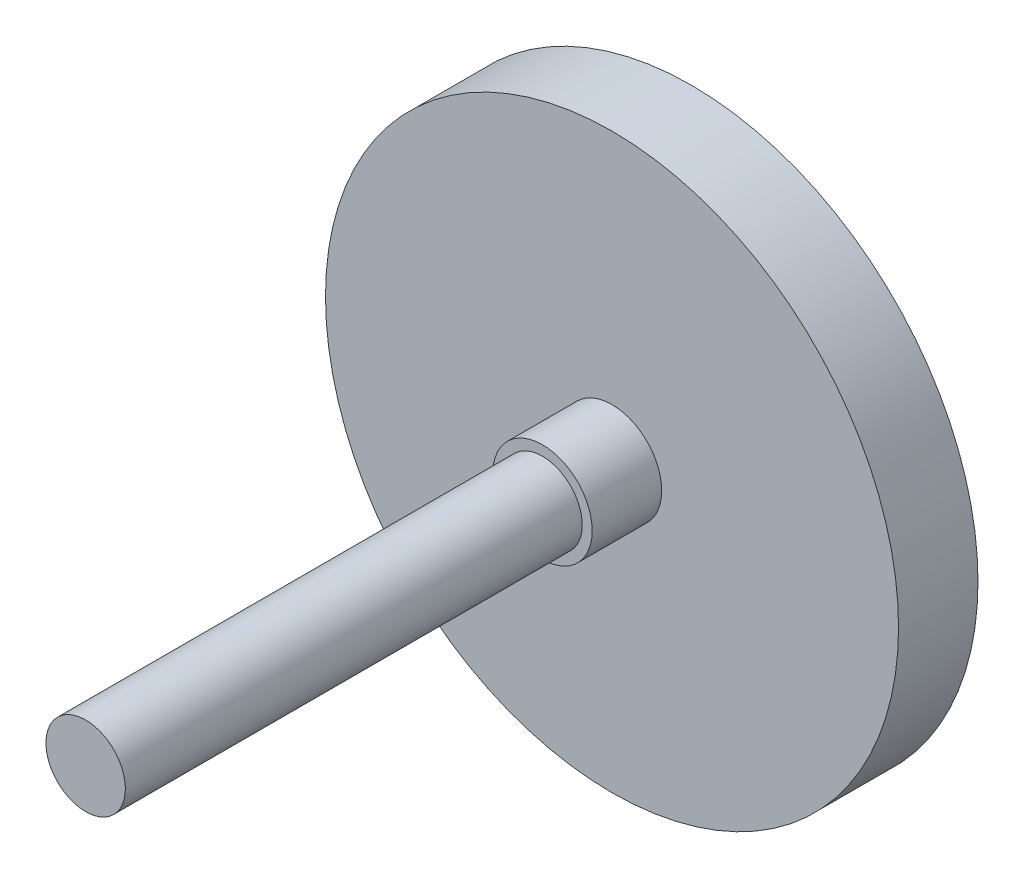
SolidWorks part; units mm, degrees
ref_plane "Plan de face" through (0, 0, 0) normal (0, 0, 1) x (1, 0, 0)
ref_plane "Plan de dessus" through (0, 0, 0) normal (0, 1, 0) x (1, 0, 0)
ref_plane "Plan de droite" through (0, 0, 0) normal (1, 0, 0) x (0, 0, -1)
sketch "Esquisse1" plane through (0, 0, 0) normal (0, 0, 1) x (1, 0, 0)
  circle A0 centre (0, 0) radius 28.85
extrude "Boss.-Extru.1" add sketch "Esquisse1" along normal blind 8
sketch "Esquisse2" plane through (0, 0, 8) normal (0, 0, 1) x (1, 0, 0)
  circle A0 centre (0, 0) radius 4
  circle A1 centre (0, 0) radius 5
sketch "Esquisse3" plane through (0, 0, 0) normal (0, 0, -1) x (-1, 0, 0)
  circle A0 centre (0, 0) radius 4
extrude "Enlèv. mat.-Extru.1" cut sketch "Esquisse3" against normal blind 2
extrude "Boss.-Extru.2" add sketch "Esquisse2" along normal blind 7
extrude "Boss.-Extru.3" add sketch "Esquisse2<2>" along normal blind 2
sketch "Esquisse2<2>" plane through (0, 0, 8) normal (0, 0, 1) x (1, 0, 0) same geometry as "Esquisse2"
extrude "Boss.-Extru.4" add sketch "Esquisse2<3>" along normal blind 4
sketch "Esquisse2<3>" plane through (0, 0, 8) normal (0, 0, 1) x (1, 0, 0) same geometry as "Esquisse2"
sketch "Esquisse4" plane through (0, 0, 8) normal (0, 0, 1) x (1, 0, 0)
  circle A0 centre (0, 0) radius 4
extrude "Boss.-Extru.6" add sketch "Esquisse4" along normal blind 53
